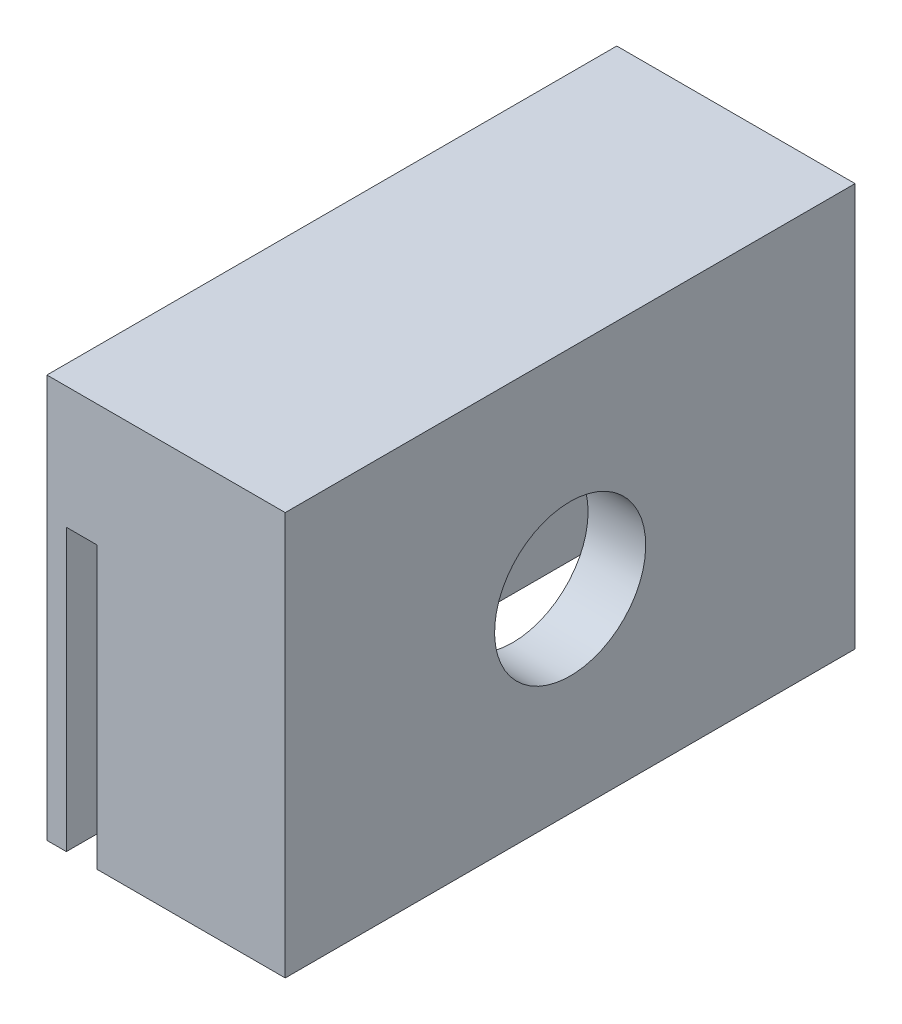
SolidWorks part; units mm, degrees
material "Custom Plastic"
ref_plane "X-Y Datum" through (0, 0, 0) normal (0, 0, 1) x (1, 0, 0)
ref_plane "X-Z Datum" through (0, 0, 0) normal (0, 1, 0) x (1, 0, 0)
ref_plane "Y-Z Datum" through (0, 0, 0) normal (1, 0, 0) x (0, 0, -1)
sketch "Sketch1" plane through (0, 0, 0) normal (0, 0, 1) x (1, 0, 0)
  line L1 (-11.825, 20) -> (11.825, 20)
  line L2 (-11.825, 20) -> (-11.825, -20)
  line L3 (-11.825, -20) -> (11.825, -20)
  line L4 (11.825, 20) -> (11.825, -20)
  line L5 (-11.825, 20) -> (11.825, -20) construction
  line L6 (-11.825, -20) -> (11.825, 20) construction
  point P0 (0, 0)
  dimension "D1" = 23.65
  dimension "D2" = 40
extrude "Boss-Extrude1" add sketch "Sketch1" along normal blind 56.55
sketch "Sketch2" plane through (0, 0, 56.55) normal (0, 0, 1) x (1, 0, 0)
  line L0 (-9.3955, -7.38) -> (-7.3635, -7.38) construction
  line L1 (-7.3635, -7.38) -> (-7.3635, 7.38) construction
  line L2 (-9.3955, 7.38) -> (-7.3635, 7.38) construction
  line L3 (-9.3955, 7.38) -> (-9.3955, -7.38) construction
  line L4 (-9.3955, -7.38) -> (-7.3635, -7.38)
  line L5 (-7.3635, -7.38) -> (-7.3635, 7.38)
  line L6 (-9.3955, 7.38) -> (-7.3635, 7.38)
  line L7 (-9.3955, 7.38) -> (-9.3955, -7.38)
  line L8 (-6.8635, -7.88) -> (-6.8635, 7.88)
  line L9 (-9.8955, 7.88) -> (-6.8635, 7.88)
  line L10 (-9.8955, 7.88) -> (-9.8955, -7.88)
  line L11 (-9.8955, -7.88) -> (-6.8635, -7.88)
  line L12 (-9.8955, -7.88) -> (-9.8955, -20)
  line L13 (-11.825, -20) -> (11.825, -20) construction
  line L14 (-6.8635, 7.88) -> (6.1045, 7.88)
  line L15 (6.1045, 7.88) -> (6.1045, -20)
  line M5 (-11.825, -20) -> (11.825, -20)
  dimension "D2" = 16
  dimension "D1" = 0.5
extrude "Cut-Extrude1" cut sketch "Sketch2" against normal through all contours L15 L14 L8 L11 L12 M5 | L10 L11 L8 L9 L7 L6 L5 L4 | L6 L7 L4 L5 region at (-8.3795, 0, 56.55) region at (-8.3795, -7.7195, 56.55) region at (-1.1176, -6.787, 56.55)
sketch "Sketch3" plane through (11.825, 0, 0) normal (1, 0, 0) x (0, 0, -1)
  line L0 (-28.275, 20) -> (-28.275, -20) construction
  line L1 (-56.55, 20) -> (0, 20) construction
  line L2 (-56.55, -20) -> (0, -20) construction
  circle A0 centre (-28.275, -0.6869) radius 7.5
  dimension "D1" = 15
extrude "Cut-Extrude2" cut sketch "Sketch3" against normal up to surface (5.7205 mm away) up to face at (6.1045, -6.06, 28.275)
sketch "Sketch4" plane through (0, 7.88, 0) normal (0, -1, 0) x (1, 0, 0)
  line L0 (-7.3635, 60.868) -> (-7.3635, 33.69) construction
  line L1 (-7.3635, 60.868) -> (-7.3635, 33.69) construction
  line L2 (-9.8955, 56.55) -> (6.1045, 56.55) construction
  line L3 (-9.8955, 56.55) -> (6.1045, 56.55)
  line L4 (-6.8635, 60.868) -> (-6.8635, 33.69)
  line L5 (-7.3635, 56.55) -> (3.7407, 56.55)
  line L7 (-6.8635, 46.55) -> (6.1045, 46.55)
  line L10 (6.1045, 0) -> (6.1045, 56.55) construction
  point P10 (-6.8635, 46.55)
  point P11 (6.1045, 46.8334)
  point P14 (0, 0)
  line M10 (6.1045, 56.55) -> (-9.8955, 56.55)
  line M13 (6.1045, 0) -> (6.1045, 56.55)
  dimension "D1" = 10
  dimension "D2" = 0.5
extrude "Boss-Extrude2" add sketch "Sketch4" along normal up to surface (27.88 mm away) contours L4 L7 L3 M13 M10 region at (-0.3795, 7.88, 51.55) up to face at (8.9647, -20, 28.275)
